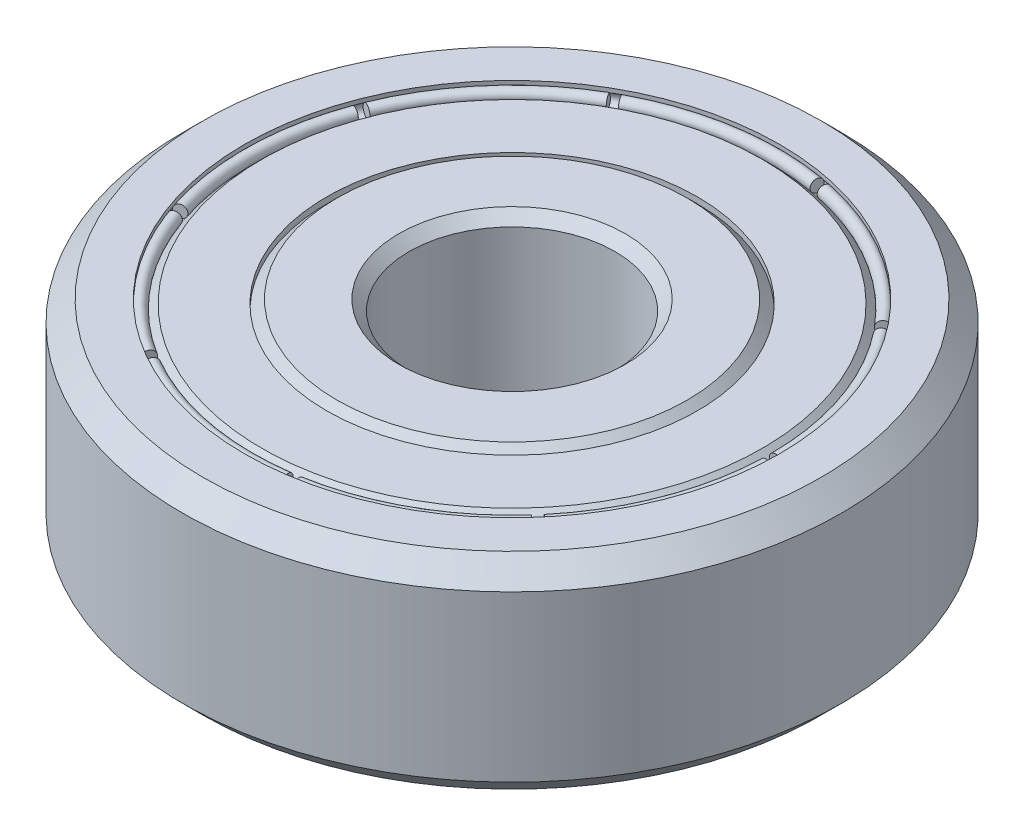
SolidWorks part; units mm, degrees
ref_plane "Front Plane" through (0, 0, 0) normal (0, 0, 1) x (1, 0, 0)
ref_plane "Top Plane" through (0, 0, 0) normal (0, 1, 0) x (1, 0, 0)
ref_plane "Right Plane" through (0, 0, 0) normal (1, 0, 0) x (0, 0, -1)
sketch "Sketch1" plane through (0, 0, 0) normal (0, 0, 1) x (1, 0, 0)
  line L0 (2.5, -2.25) -> (2.5, 2.25)
  line L1 (2.75, 2.5) -> (4.25, 2.5)
  line L2 (8, 2) -> (8, -2)
  line L3 (7.5, -2.5) -> (6.5, -2.5)
  line L4 (0, 0) -> (0, 2.5) construction
  line L5 (7.5, 2.5) -> (8, 2)
  line L6 (8, -2) -> (7.5, -2.5)
  line L7 (2.5, 0) -> (8, 0) construction
  line L8 (6.5, -2.5) -> (6.5, -2.4)
  line L9 (6.2879, -2.1879) -> (6.0757, -2.4)
  line L10 (6.0757, -2.4) -> (4.5, -2.4)
  line L11 (4.5, -2.4) -> (4.5, -2.25)
  line L12 (4.5, -2.25) -> (4.25, -2.5)
  line L13 (4.25, -2.5) -> (2.75, -2.5)
  line L14 (6.5, 2.5) -> (6.5, 2.4)
  line L15 (4.5, 2.25) -> (4.25, 2.5)
  line L16 (4.5, 2.4) -> (4.5, 2.25)
  line L17 (6.0757, 2.4) -> (4.5, 2.4)
  line L18 (6.2879, 2.1879) -> (6.0757, 2.4)
  line L19 (6.5, 2.5) -> (7.5, 2.5)
  line L20 (2.75, 2.5) -> (2.5, 2.25)
  line L21 (2.5, -2.25) -> (2.75, -2.5)
  line L22 (6.2879, -2.1879) -> (6.5, -2.4) construction
  arc A0 (6.5, -2.4) -> (6.2879, -2.1879) centre (6.3939, -2.2939) ccw
  arc A1 (6.5, 2.4) -> (6.2879, 2.1879) centre (6.3939, 2.2939) cw
  point P0 (0, 0)
  dimension "D10" = 0.15
  dimension "D1" = 5
  dimension "D2" = 16
  dimension "D3" = 5
  dimension "D4" = 0.5
  dimension "D5" = 13
  dimension "D6" = 9
  dimension "D7" = 0.1
  dimension "D8" = 8.5
  dimension "D11" = 0.1
  dimension "D12" = 0.25
revolve "Revolve1" add sketch "Sketch1" angle 360 about L4
sketch "Sketch2" plane through (0, 0, 0) normal (0, 0, 1) x (1, 0, 0)
  circle A0 centre (6.3939, -2.2939) radius 0.15
  arc A1 (6.5, -2.4) -> (6.2879, -2.1879) centre (6.3939, -2.2939) ccw construction
revolve "Revolve2" add sketch "Sketch2" angle 38 about L4
pattern_circular "CirPattern1" count 9 over 360 about axis through (0, 0, 0) along (0, -1, 0) reverse direction yes of bodies 102
mirror "Mirror1" about plane through (0, 0, 0) normal (0, 1, 0) of bodies 102 110 109 108 107 106 105 104 103
